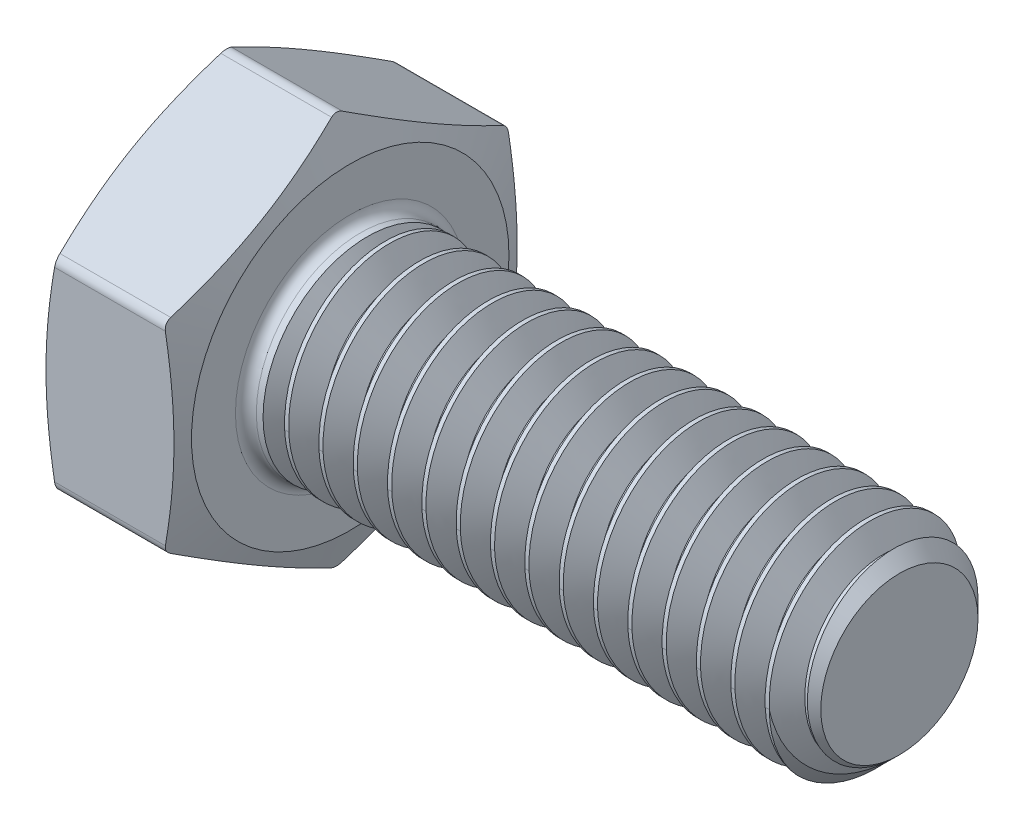
SolidWorks part; units mm, degrees
ref_plane "Front Plane" through (0, 0, 0) normal (0, 0, 1) x (1, 0, 0)
ref_plane "Top Plane" through (0, 0, 0) normal (0, 1, 0) x (1, 0, 0)
ref_plane "Right Plane" through (0, 0, 0) normal (1, 0, 0) x (0, 0, -1)
sketch "Sketch1" plane through (0, 0, 0) normal (0, 0, 1) x (1, 0, 0)
  line L0 (0, 0) -> (12.7, 0) construction
  line L1 (0, 0) -> (-3.175, 0) construction
  line L2 (0, 3.9688) -> (0, -3.9688) construction
  line L3 (-3.175, 3.9688) -> (-3.175, -3.9688) construction
  line L4 (12.7, 2.413) -> (12.7, -2.413) construction
  line L8 (11.9062, 2.413) -> (12.7, 2.413) construction
  point P8 (11.9062, 0)
  point P11 (9.9219, -2.413)
  point P12 (0.3969, 0)
  dimension "Head Height" = 3.175
  dimension "Head Width" = 7.9375
  dimension "Length" = 12.7
  dimension "Thread Size" = 4.826
  dimension "D1" = 2.7781
  dimension "Thread Pitch" = 0.7937
  dimension "D2" = 0.3969
sketch "Sketch2" plane through (0, 0, 0) normal (1, 0, 0) x (0, 0, -1)
  circle A0 centre (0, 0) radius 2.413
extrude "Boss-Extrude1" add sketch "Sketch2" along normal up to vertex (12.7 mm away) up to point (12.7, 2.413, 0)
sketch "Sketch3" plane through (0, 0, 0) normal (-1, 0, 0) x (0, 0, 1)
  line L0 (0, 4.5827) -> (0, 0) construction
  line L1 (0, 4.5827) -> (-3.9688, 2.2914)
  line L2 (-3.9688, 2.2914) -> (-3.9688, -2.2914)
  line L3 (-3.9688, -2.2914) -> (0, -4.5827)
  line L4 (0, -4.5827) -> (3.9688, -2.2914)
  line L5 (3.9688, -2.2914) -> (3.9688, 2.2914)
  line L6 (3.9688, 2.2914) -> (0, 4.5827)
  circle A0 centre (0, 0) radius 3.9688 construction
extrude "Boss-Extrude2" add sketch "Sketch3" along normal up to vertex (3.175 mm away) up to point (-3.175, 3.9688, 0)
sketch "Sketch5" plane through (-3.175, 0, 0) normal (-1, 0, 0) x (0, 0, 1)
  circle A0 centre (0, 0) radius 3.9688 construction
  circle A1 centre (0, 0) radius 3.9688 construction
  circle A2 centre (0, 0) radius 3.6711
  dimension "D1" = 0.2977
extrude "Cut-Extrude1" cut sketch "Sketch5" against normal up to vertex (3.175 mm away) draft 70 flip side to cut up to point (0, 0, 0)
sketch "Sketch15" plane through (0, 0, 0) normal (1, 0, 0) x (0, 0, -1)
  circle A1 centre (0, 0) radius 3.6711
  circle A2 centre (0, 0) radius 3.6711
  dimension "D1" = 0
extrude "Cut-Extrude2" cut sketch "Sketch15" against normal through all draft 70 flip side to cut
fillet "Fillet7" radius 0.248 6 edges at (-1.5875, -4.5827, 0) (-1.5875, -2.2914, -3.9688) (-1.5875, 2.2914, -3.9688) (-1.5875, 4.5827, 0) (-1.5875, -2.2914, 3.9688) (-1.5875, 2.2914, 3.9688)
chamfer "Chamfer1" distance 0.5953 angle 45 1 edges at (12.7, 0, -2.413)
fillet "Fillet4" radius 0.2413 1 edges at (0, 0, 2.413)
sketch "Reference Sketch1" plane through (0, 0, 0) normal (1, 0, 0) x (0, 0, -1)
  line L1 (0, 4.5827) -> (-3.9688, 2.2914)
  line L2 (-3.9688, 2.2914) -> (-3.9688, -2.2914)
  line L3 (-3.9688, -2.2914) -> (0, -4.5827)
  line L4 (0, -4.5827) -> (3.9687, -2.2914)
  line L5 (3.9687, -2.2914) -> (3.9688, 2.2914)
  line L6 (3.9688, 2.2914) -> (0, 4.5827)
  circle A0 centre (0, 0) radius 3.9688 construction
  circle A1 centre (0, 0) radius 3.9688
sketch "Sketch12" plane through (12.7, 0, 0) normal (1, 0, 0) x (0, 0, -1)
  circle A1 centre (0, 0) radius 2.413
ref_plane "Plane2" through (0.3969, 0, 0) normal (1, 0, 0) x (0, 0, -1)
split "Split1" trim tools "Plane2" bodies to split 127 116 resulting bodies 118 119
curve "Helix/Spiral2" pitch 0.7937 height 13.4937 radius 2.413 centre (12.7, 0, 0) axis (-1, 0, 0) start towards (0, 1, 0) parameters "Pitch"=0.7937
sketch "Sketch13" plane through (0, 0, 0) normal (0, 0, 1) x (1, 0, 0)
  line L0 (12.7, 2.413) -> (13.3985, 2.413)
  line L1 (12.7, -2.413) -> (12.7, 2.413) construction
  line L2 (13.3985, 2.413) -> (13.0969, 1.8906)
  line L3 (13.0969, 1.8906) -> (13.0016, 1.8906)
  line L4 (13.0016, 1.8906) -> (12.7, 2.413)
  line L5 (13.0492, 2.413) -> (13.0492, 1.8906) construction
  line L6 (12.8508, 2.1518) -> (13.2477, 2.1518) construction
  dimension "D1" = 60
  dimension "D2" = 0.0953
  dimension "D3" = 0.3969
sweep "Cut-Sweep1" cut profiles "Sketch13" path "Helix/Spiral2" align with end faces yes
sketch "Sketch14" plane through (0.3969, 0, 0) normal (1, 0, 0) x (0, 0, -1)
  circle A1 centre (0, 0) radius 2.413
  circle A2 centre (0, 0) radius 2.413
  dimension "D1" = 0
extrude "Boss-Extrude4" add sketch "Sketch14" along normal through all draft 59
equation "\"D3@Helix/Spiral2\"=\"Length@Sketch1\" + \"Thread Pitch@Sketch1\""
equation "\"D1@Chamfer1\"=\"Thread Pitch@Sketch1\"*0.750"
equation "\"D1@Sketch1\"=\"Thread Pitch@Sketch1\"*3.5"
equation "\"Pitch@Helix/Spiral2\"=\"Thread Pitch@Sketch1\""
equation "\"D1@Sketch5\"=(\"Head Width@Sketch1\"*0.075)/2"
equation "\"D1@Fillet4\"=\"Thread Size@Sketch1\"*0.05"
equation "\"D2@Sketch1\" = \"Thread Pitch@Sketch1\"*.5"
equation "\"D1@Fillet7\"=\"Head Width@Sketch1\"*0.03125"
equation "\"D2@Sketch13\"=\"Thread Pitch@Sketch1\"*.12"
equation "\"D3@Sketch13\"=\"Thread Pitch@Sketch1\"*.5"
